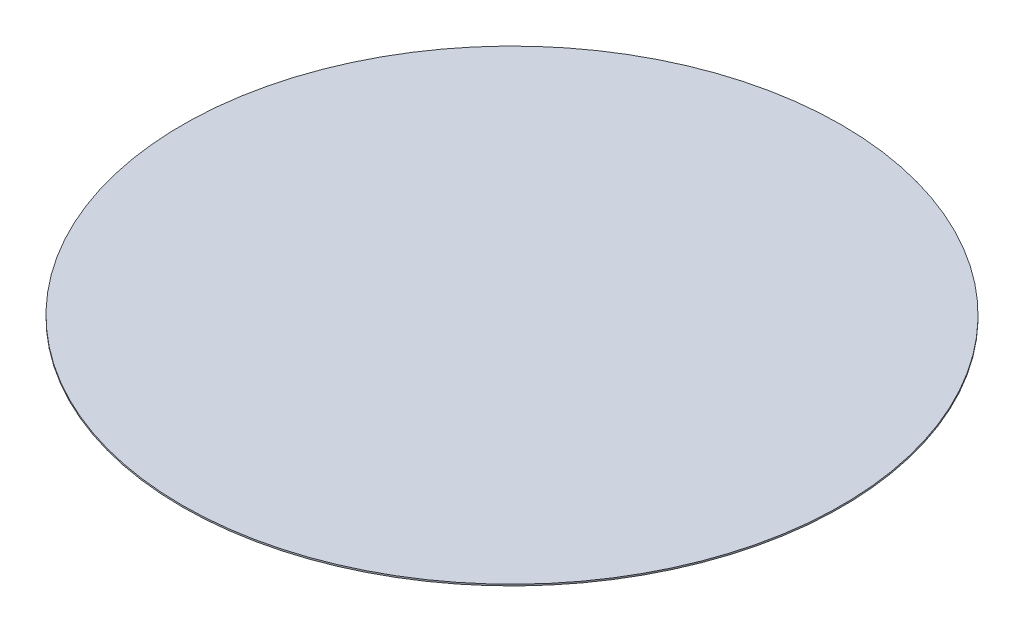
SolidWorks part; units mm, degrees
ref_plane "Front" through (0, 0, 0) normal (0, 0, 1) x (1, 0, 0)
ref_plane "Top" through (0, 0, 0) normal (0, 1, 0) x (1, 0, 0)
ref_plane "Right" through (0, 0, 0) normal (1, 0, 0) x (0, 0, -1)
sketch "Sketch1" plane through (0, 0, 0) normal (0, 1, 0) x (1, 0, 0)
  circle A0 centre (0, 0) radius 11
  dimension "D1" = 22
extrude "Boss-Extrude1" add sketch "Sketch1" along normal blind 0.05
